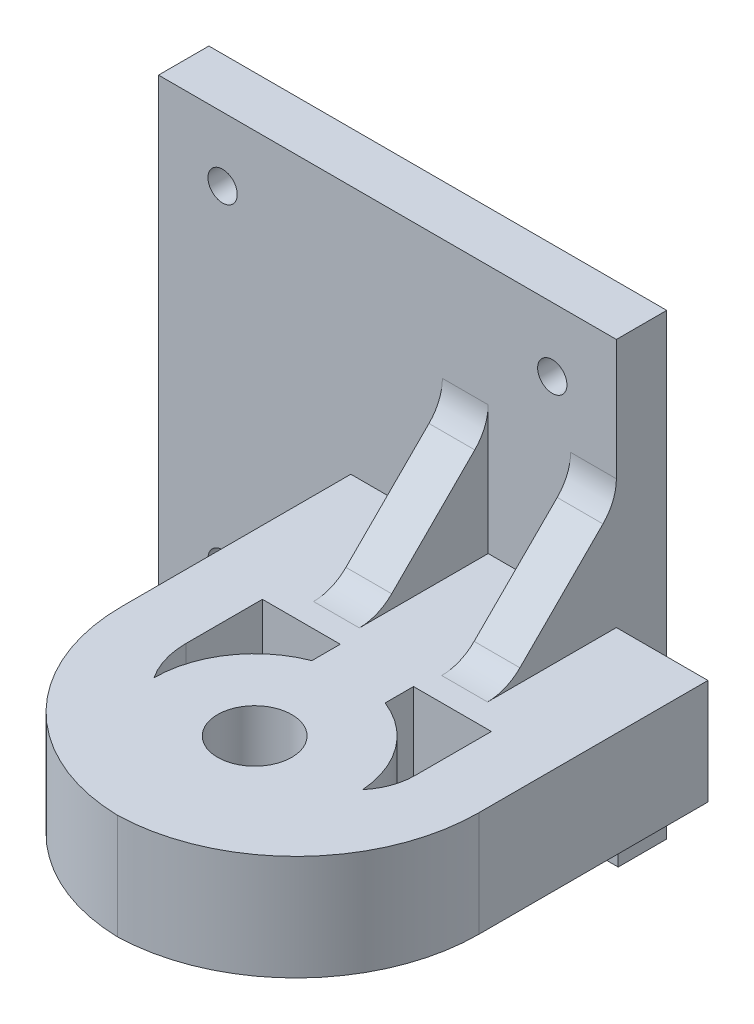
SolidWorks part; units mm, degrees
ref_plane "Front Plane" through (0, 0, 0) normal (0, 0, 1) x (1, 0, 0)
ref_plane "Top Plane" through (0, 0, 0) normal (0, 1, 0) x (1, 0, 0)
ref_plane "Right Plane" through (0, 0, 0) normal (1, 0, 0) x (0, 0, -1)
sketch "Sketch1" plane through (0, 0, 0) normal (0, 1, 0) x (1, 0, 0)
  line L1 (0, 0) -> (39, 0)
  line L2 (0, 0) -> (0, 45)
  line L3 (0, 45) -> (39, 45)
  line L4 (39, 0) -> (39, 45)
  dimension "D1" = 39
  dimension "D2" = 45
extrude "Boss-Extrude1" add sketch "Sketch1" along normal blind 12.5
sketch "Sketch2" plane through (0, 12.5, 0) normal (0, 1, 0) x (1, 0, 0)
  line L0 (19.5, 45) -> (19.5, 0) construction
  line L1 (39, 45) -> (0, 45) construction
  line L2 (0, 0) -> (39, 0) construction
  circle A0 centre (19.5, 15) radius 4.05
  dimension "D2" = 8.1
  dimension "D1" = 30
extrude "Cut-Extrude1" cut sketch "Sketch2" against normal through all
sketch "Sketch3" plane through (0, 0, -45) normal (0, 0, -1) x (-1, 0, 0)
  line L0 (-19.5, 12.5) -> (-19.5, 0) construction
  line L1 (-29, -10.25) -> (21, -10.25)
  line L2 (-29, -10.25) -> (-29, 39.75)
  line L3 (-29, 39.75) -> (21, 39.75)
  line L4 (21, -10.25) -> (21, 39.75)
  line L5 (-39, 12.5) -> (0, 12.5) construction
  line L6 (-39, 0) -> (0, 0) construction
  line L7 (-39, 6.25) -> (0, 6.25) construction
  line L8 (-39, 12.5) -> (-39, 0) construction
  line L9 (0, 12.5) -> (0, 0) construction
  dimension "D1" = 50
  dimension "D2" = 9.5
  dimension "D3" = 50
  dimension "D4" = 16.5
extrude "Boss-Extrude2" add sketch "Sketch3" along normal blind 5.5
sketch "Sketch4" plane through (39, 0, 0) normal (1, 0, 0) x (0, 0, -1)
  line L0 (33, 12.5) -> (45, 24.5)
  line L1 (0, 12.5) -> (45, 12.5) construction
  line L2 (45, 39.75) -> (45, 12.5) construction
  line L3 (45, 24.5) -> (45, 12.5)
  line L4 (45, 12.5) -> (45, 0) construction
  line L5 (45, 12.5) -> (33, 12.5)
  dimension "D1" = 12
  dimension "D2" = 12
extrude "Boss-Extrude3" add sketch "Sketch4" against normal blind 5 from offset 10 offset against normal yes
pattern_linear "LPattern1" count 2 spacing 14 along (-1, 0, 0) of "Boss-Extrude3"
fillet "Fillet1" radius 5 4 edges at (26.5, 24.5, -45) (12.5, 24.5, -45) (12.5, 12.5, -33) (26.5, 12.5, -33)
sketch "Sketch5" plane through (0, 0, -50.5) normal (0, 0, -1) x (-1, 0, 0)
  line L0 (-4, 39.75) -> (-4, -10.25) construction
  line L1 (21, 39.75) -> (-29, 39.75) construction
  line L2 (-29, -10.25) -> (21, -10.25) construction
  line L3 (-29, 14.75) -> (21, 14.75) construction
  line L4 (-29, 39.75) -> (-29, -10.25) construction
  line L5 (21, -10.25) -> (21, 39.75) construction
  circle A0 centre (-22, 32.75) radius 1.6
  circle A1 centre (14, 32.75) radius 1.6
  circle A2 centre (14, -3.25) radius 1.6
  circle A3 centre (-22, -3.25) radius 1.6
  dimension "D5" = 3.2
  dimension "D6" = 3.2
  dimension "D7" = 3.2
  dimension "D8" = 3.2
  dimension "D1" = 36
  dimension "D2" = 36
  dimension "D3" = 7
  dimension "D4" = 7
extrude "Cut-Extrude2" cut sketch "Sketch5" against normal through all
fillet "Fillet2" radius 20 2 edges at (0, 6.25, 0) (39, 6.25, 0)
sketch "Sketch6" plane through (0, 12.5, 0) normal (0, 1, 0) x (1, 0, 0)
  line L0 (0, 20) -> (39, 20) construction
  line L1 (0, 45) -> (0, 20) construction
  line L2 (39, 20) -> (39, 45) construction
  line L3 (7, 20) -> (7, 28.3476)
  line L4 (7, 28.3476) -> (15.5, 28.3476)
  line L5 (15.5, 28.3476) -> (15.5, 25.247)
  line L6 (23.5, 25.247) -> (23.5, 28.3476)
  line L7 (23.5, 28.3476) -> (32, 28.3476)
  line L8 (32, 28.3476) -> (32, 20)
  arc A0 (8.5, 15) -> (15.5, 25.247) centre (19.5, 15) cw
  arc A1 (30.4703, 15.8083) -> (23.5, 25.247) centre (19.5, 15) ccw
  arc A2 (19.5, 0.0063) -> (39, 20) centre (19, 20) ccw construction
  arc A3 (8.5, 15) -> (7, 20) centre (16.0833, 20) cw
  arc A4 (30.4703, 15.8083) -> (32, 20) centre (25.4923, 20) ccw
  dimension "D1" = 11
  dimension "D2" = 11
  dimension "D3" = 4
  dimension "D4" = 4
  dimension "D5" = 7
  dimension "D6" = 7
extrude "Cut-Extrude3" cut sketch "Sketch6" against normal through all
sketch "Sketch7" plane through (0, 0, 0) normal (0, -1, 0) x (1, 0, 0)
  line L0 (0, -45) -> (39, -45)
  line L1 (39, -45) -> (39, 5.0637)
  line L2 (39, 5.0637) -> (0, 5.0637)
  line L3 (0, 5.0637) -> (0, -45)
  line L4 (19.5, -10.95) -> (19.5, -19.05) construction
  line L5 (15.5, -28.3476) -> (15.5, -25.247) construction
  line L6 (4.5, -43.0018) -> (15.5, -43.0018)
  line L7 (4.5, -43.0018) -> (4.5, -32.0018)
  line L8 (4.5, -32.0018) -> (15.5, -32.0018)
  line L9 (15.5, -43.0018) -> (15.5, -32.0018)
  line L10 (23.5, -43.0018) -> (34.5, -43.0018)
  line L11 (23.5, -43.0018) -> (23.5, -32.0018)
  line L12 (23.5, -32.0018) -> (34.5, -32.0018)
  line L13 (34.5, -43.0018) -> (34.5, -32.0018)
  line L14 (23.5, -25.247) -> (23.5, -28.3476) construction
  line L15 (0, -45) -> (0, -20) construction
  line L16 (39, -20) -> (39, -45) construction
  circle A0 centre (19.5, -15) radius 4.05 construction
  circle A1 centre (19.5, -15) radius 11
  dimension "D1" = 22
  dimension "D2" = 11
  dimension "D3" = 11
  dimension "D4" = 11
  dimension "D5" = 11
extrude "Cut-Extrude4" cut sketch "Sketch7" against normal blind 1
sketch "Sketch8" plane through (0, 0, -50.5) normal (0, 0, -1) x (-1, 0, 0)
  line L0 (21, 39.75) -> (-29, 39.75) construction
  line L1 (-16.5, 35.25) -> (8.5, 35.25)
  line L2 (-16.5, 35.25) -> (-16.5, 30.25)
  line L3 (-16.5, 30.25) -> (8.5, 30.25)
  line L4 (8.5, 35.25) -> (8.5, 30.25)
  line L5 (-4, 39.75) -> (-4, -10.25) construction
  line L6 (-29, -10.25) -> (21, -10.25) construction
  line L7 (21, -10.25) -> (21, 39.75) construction
  line L8 (11.5, 27.25) -> (16.5, 27.25)
  line L9 (11.5, 27.25) -> (11.5, 2.25)
  line L10 (11.5, 2.25) -> (16.5, 2.25)
  line L11 (16.5, 27.25) -> (16.5, 2.25)
  line L12 (21, 14.75) -> (-29, 14.75) construction
  line L13 (-29, 39.75) -> (-29, -10.25) construction
  line L15 (8.5, -0.75) -> (-16.5, -0.75)
  line L16 (8.5, -0.75) -> (8.5, -5.75)
  line L17 (8.5, -5.75) -> (-16.5, -5.75)
  line L18 (-16.5, -0.75) -> (-16.5, -5.75)
  line L19 (-19.5, 27.25) -> (-24.5, 27.25)
  line L20 (-19.5, 27.25) -> (-19.5, 2.25)
  line L21 (-19.5, 2.25) -> (-24.5, 2.25)
  line L22 (-24.5, 27.25) -> (-24.5, 2.25)
  dimension "D1" = 5
  dimension "D2" = 4.5
  dimension "D3" = 25
  dimension "D4" = 12.5
  dimension "D5" = 4.5
  dimension "D6" = 5
  dimension "D7" = 25
  dimension "D8" = 12.5
  dimension "D9" = 4.5
  dimension "D10" = 5
  dimension "D11" = 25
  dimension "D12" = 12.5
  dimension "D13" = 4.5
  dimension "D14" = 5
  dimension "D15" = 25
  dimension "D16" = 12.5
extrude "Boss-Extrude4" add sketch "Sketch8" along normal blind 0.5
sketch "Sketch9" plane through (0, 0, -45) normal (0, 0, 1) x (1, 0, 0)
  line L0 (0, 1) -> (19.5, 1) construction
  line L1 (29, -10.25) -> (-5.8, -10.25)
  line L2 (29, -10.25) -> (29, 1)
  line L3 (29, 1) -> (-5.8, 1)
  line L4 (-5.8, -10.25) -> (-5.8, 1)
  dimension "D1" = 0
  dimension "D2" = 34.8
extrude "Cut-Extrude5" cut sketch "Sketch9" against normal blind 0.2
